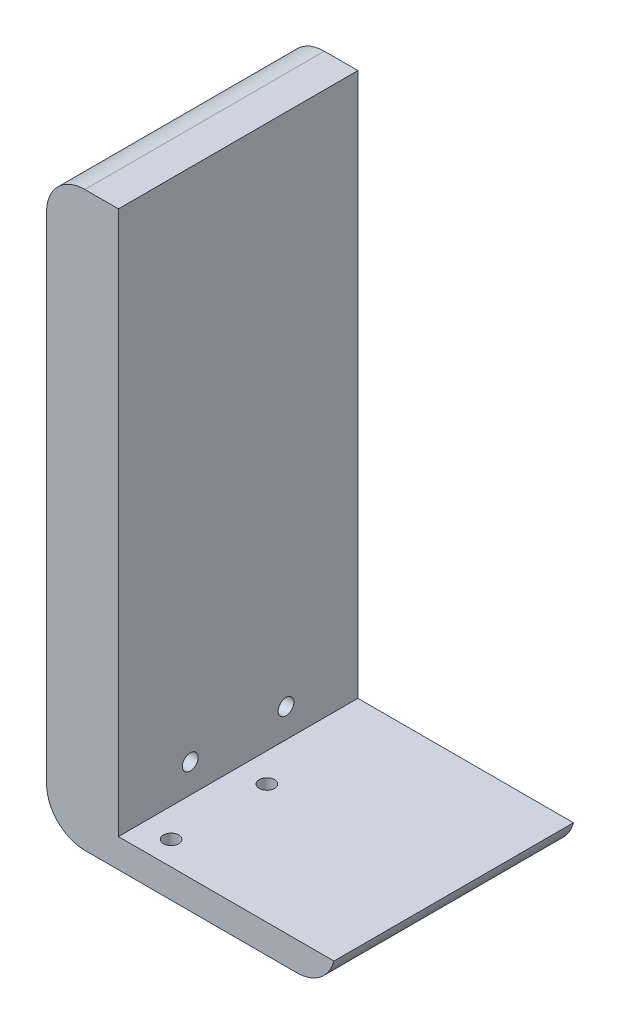
SolidWorks part; units mm, degrees
ref_plane "前视基准面" through (0, 0, 0) normal (0, 0, 1) x (1, 0, 0)
ref_plane "上视基准面" through (0, 0, 0) normal (0, 1, 0) x (1, 0, 0)
ref_plane "右视基准面" through (0, 0, 0) normal (1, 0, 0) x (0, 0, -1)
other "Configuration Table"
sketch "草图1" plane through (0, 0, 0) normal (0, 0, 1) x (1, 0, 0)
  line L0 (0, 0) -> (0, 119.5)
  line L1 (0, 119.5) -> (15, 119.5)
  line L2 (15, 119.5) -> (15, 6)
  line L3 (15, 6) -> (60, 6)
  line L4 (60, 6) -> (60, 0)
  line L5 (60, 0) -> (0, 0)
  dimension "D1" = 6
  dimension "D2" = 15
  dimension "D3" = 60
  dimension "D4" = 119.5
extrude "凸台-拉伸1" add sketch "草图1" along normal mid plane 50
fillet "圆角1" radius 8 3 edges at (0, 119.5, 0) (60, 0, 0) (0, 0, 0)
sketch "草图2" plane through (0, 0, 0) normal (-1, 0, 0) x (0, 0, 1)
  line L0 (0, 0) -> (0, 33.7003) construction
  line L2 (25, 0) -> (-25, 0) construction
  circle A0 centre (10, 12) radius 1.65
  circle A1 centre (-10, 12) radius 1.65
  dimension "D1" = 3.3
  dimension "D2" = 12
  dimension "D3" = 20
extrude "切除-拉伸1" cut sketch "草图2" against normal through all
sketch "草图3" plane through (0, 6, 0) normal (0, 1, 0) x (1, 0, 0)
  line L2 (0, -25) -> (0, 25) construction
  line L3 (60, -25) -> (15, -25) construction
  circle A0 centre (21, -20) radius 1.6
  circle A1 centre (21, 0) radius 1.6
  dimension "D1" = 3.2
  dimension "D2" = 20
  dimension "D3" = 21
  dimension "D4" = 5
extrude "切除-拉伸2" cut sketch "草图3" against normal through all
